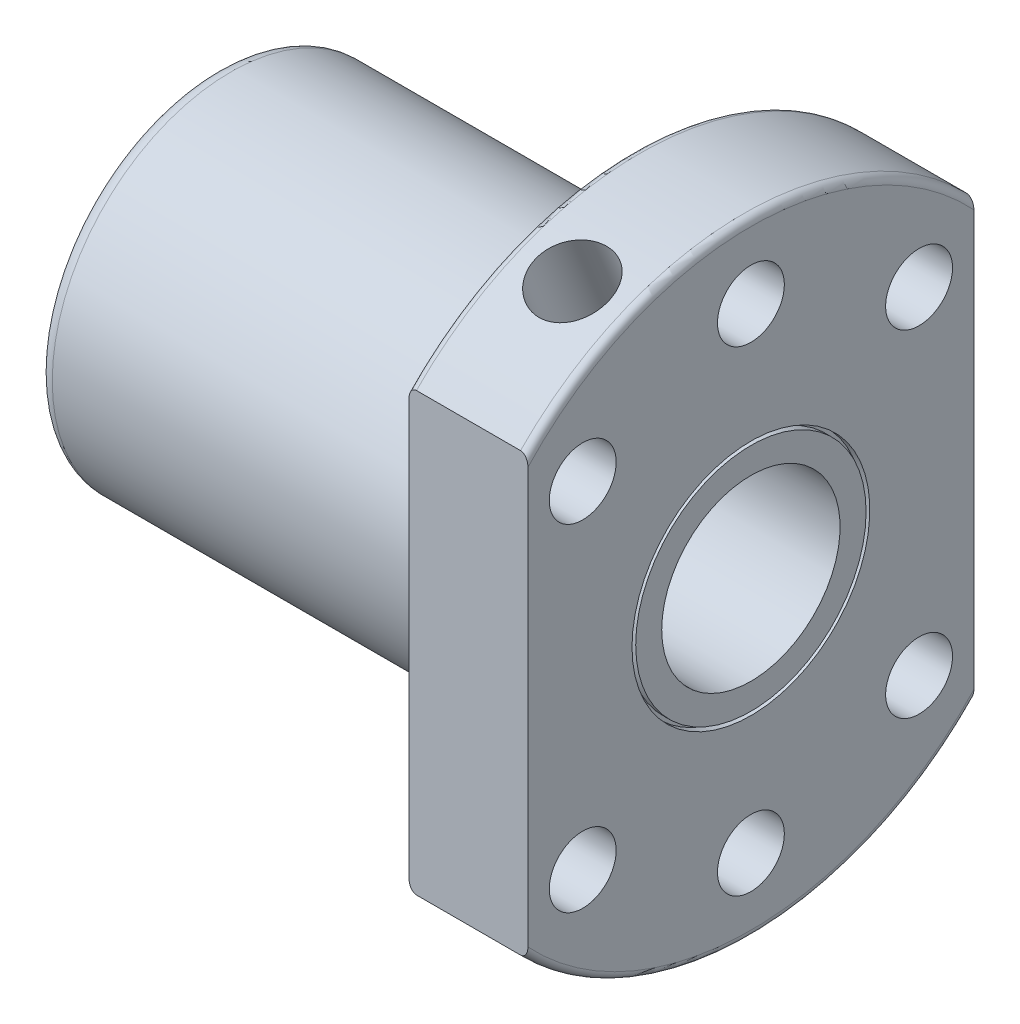
SolidWorks part; units mm, degrees
ref_plane "Front Plane" through (0, 0, 0) normal (0, 0, 1) x (1, 0, 0)
ref_plane "Top Plane" through (0, 0, 0) normal (0, 1, 0) x (1, 0, 0)
ref_plane "Right Plane" through (0, 0, 0) normal (1, 0, 0) x (0, 0, -1)
ref_axis "Axis_X" through (-29.8, 0, 0) along (1, 0, 0)
ref_axis "Axis_Y" through (0, 23.1, 0) along (0, -1, 0)
ref_axis "Axis_Z" through (0, 0, -16.5) along (0, 0, 1)
sketch "Sketch1" plane through (0, 0, 0) normal (0, 0, 1) x (1, 0, 0)
  line L0 (0, 0) -> (8, 0) construction
  line L1 (-28, 8) -> (-28, 11)
  line L2 (-27, 12) -> (0, 12)
  line L3 (0, 12) -> (0, 20.5)
  line L4 (0.5, 21) -> (7.5, 21)
  line L5 (8, 20.5) -> (8, 8)
  line L6 (-28, 8) -> (-27.5, 8)
  line L7 (-27.5, 8) -> (-27.5, 7.75)
  line L8 (-28, 6) -> (8, 6)
  line L9 (7.5, 7.75) -> (7.5, 8)
  line L10 (7.5, 8) -> (8, 8)
  line L11 (-27.5, 7.75) -> (-28, 7.75)
  line L12 (-28, 7.75) -> (-28, 6)
  line L13 (7.5, 7.75) -> (8, 7.75)
  line L14 (8, 7.75) -> (8, 6)
  arc A0 (-27, 12) -> (-28, 11) centre (-27, 11) ccw
  arc A1 (8, 20.5) -> (7.5, 21) centre (7.5, 20.5) ccw
  arc A2 (0.5, 21) -> (0, 20.5) centre (0.5, 20.5) ccw
  dimension "FIX_68" = 0.5
  dimension "FIX_78" = 1
  dimension "FIX_61" = 8
  dimension "FIX_62" = 36
  dimension "FIX_63" = 24
  dimension "FIX_64" = 42
  dimension "FIX_65" = 16
  dimension "FIX_67" = 12
  dimension "FIX_69" = 15.5
  dimension "FIX_70" = 0.5
revolve "Revolve1" add sketch "Sketch1" angle 360 about axis through (-29.8, 0, 0) along (1, 0, 0)
sketch "Sketch2" plane through (8, 0, 0) normal (1, 0, 0) x (0, 0, -1)
  line L1 (-15, 21) -> (15, 21)
  line L2 (-15, 21) -> (-15, -21)
  line L3 (-15, -21) -> (15, -21)
  line L4 (15, 21) -> (15, -21)
  circle A0 centre (0, 0) radius 21 construction
  dimension "FIX_72" = 30
extrude "Cut-Extrude1" cut sketch "Sketch2" against normal blind 10 flip side to cut
hole_wizard "DiameterHole1" positions "Sketch4" profile "Sketch3" hole size "Ø4.5" standard "JIS" end condition through all
sketch "Sketch4" plane through (8, 0, 0) normal (1, 0, 0) x (0, 0, -1)
  line L0 (0, 0) -> (-11.3137, 11.3137) construction
  line L2 (0, 0) -> (11.3137, 11.3137) construction
  line L4 (0, 0) -> (0, 16) construction
  circle A0 centre (0, 0) radius 16 construction
  point P0 (11.3137, 11.3137)
  point P2 (0, 16)
  point P4 (-11.3137, 11.3137)
  point P6 (-11.3137, -11.3137)
  point P8 (0, -16)
  point P10 (11.3137, -11.3137)
  dimension "FIX_74" = 32
  dimension "FIX_75" = 45
  dimension "FIX_76" = 45
sketch "Sketch3" plane through (8, 11.3137, -11.3137) normal (0, 1, 0) x (0, 0, -1)
  line L0 (0, 0) -> (0, 36)
  line L1 (0, 36) -> (2.25, 36)
  line L2 (2.25, 36) -> (2.25, 0)
  line L5 (2.25, 0) -> (0, 0)
  line L11 (0, -6.35) -> (0, 107.95) construction
  dimension "FIX_77" = 4.5
  dimension "Thru Hole Depth" = 36
ref_plane "Plane1" through (0, 19.4015, 8.0364) normal (0, 0.9239, 0.3827) x (1, 0, 0)
hole_wizard "Tap1" positions "Sketch6" profile "Sketch5" hole size "M6x1.0" standard "JIS" end condition up to next
sketch "Sketch6" plane through (0, 19.4015, 8.0364) normal (0, 0.9239, 0.3827) x (1, 0, 0)
  line L0 (0, 0) -> (4, 0) construction
  line L1 (0, 12) -> (0, -12) construction
  point P0 (4, 0)
  dimension "FIX_80" = 4
sketch "Sketch5" plane through (4, 19.4015, 8.0364) normal (1, 0, 0) x (0, -0.3827, 0.9239)
  line L0 (0, 0) -> (0, 15)
  line L1 (0, 15) -> (2.4585, 15)
  line L2 (2.4585, 15) -> (2.4585, 0)
  line L5 (2.4585, 0) -> (0, 0)
  line L11 (0, -6.35) -> (0, 107.95) construction
  dimension "FIX_81" = 4.917
  dimension "Thru Hole Depth" = 15
cosmetic thread "Thread1" parameters "FIX_83"=8, "FIX_82"=6
sketch "草图1" plane through (8, 0, 0) normal (1, 0, 0) x (0, 0, -1)
  circle A0 centre (-11.3137, 11.3137) radius 2.25
  circle A1 centre (0, 16) radius 2.25
  circle A2 centre (11.3137, 11.3137) radius 2.25
  circle A4 centre (11.3137, -11.3137) radius 2.25
  circle A5 centre (0, -16) radius 2.25
  circle A6 centre (-11.3137, -11.3137) radius 2.25
  circle A8 centre (-16, 0) radius 2.25
  circle A9 centre (16, 0) radius 2.25
  point P19 (0, 0)
  dimension "D1" = 8
equation "\"Factor\"= 1.082532"
